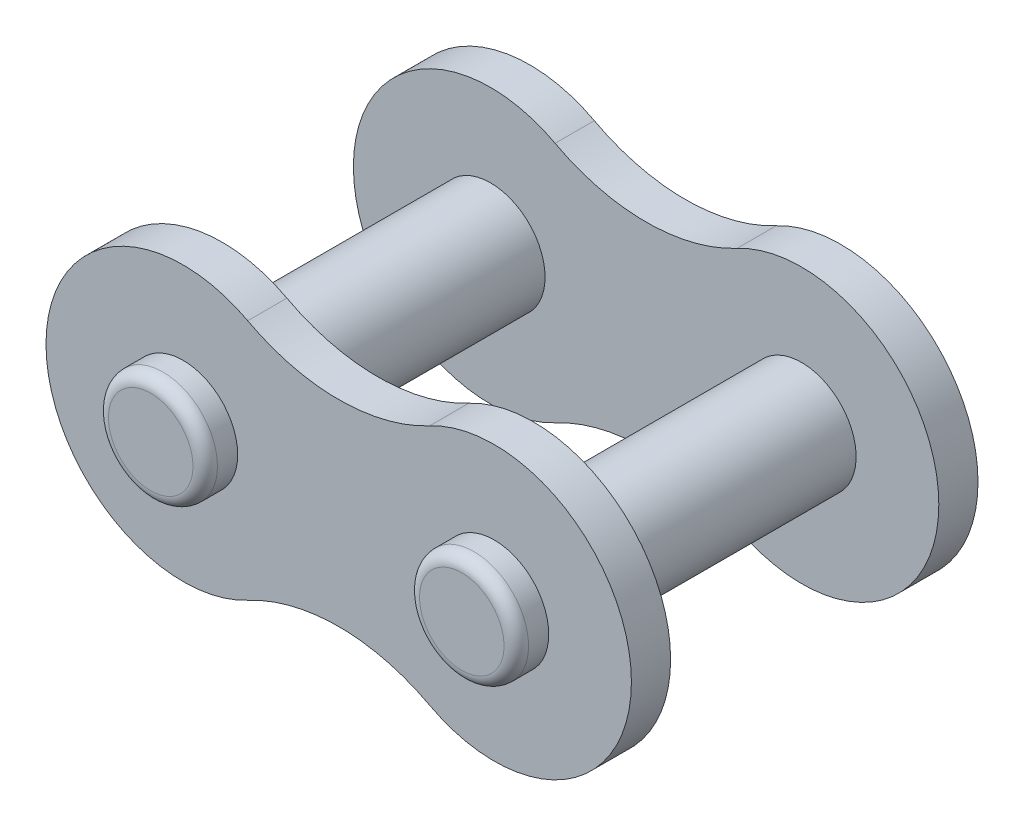
SolidWorks part; units mm, degrees
ref_plane "Front Plane" through (0, 0, 0) normal (0, 0, 1) x (1, 0, 0)
ref_plane "Top Plane" through (0, 0, 0) normal (0, 1, 0) x (1, 0, 0)
ref_plane "Right Plane" through (0, 0, 0) normal (1, 0, 0) x (0, 0, -1)
ref_axis "Axis_X" through (-19.495, 0, 0) along (1, 0, 0)
ref_axis "Axis_Y" through (0, 6.16, 0) along (0, -1, 0)
ref_axis "Axis_Z" through (0, 0, -9.24) along (0, 0, 1)
sketch "Sketch1" plane through (0, 0, 0) normal (0, 1, 0) x (1, 0, 0)
  line L0 (0, 0) -> (0, 8.4) construction
  line L1 (0, -8.4) -> (0, 8.4)
  line L2 (0, 8.4) -> (1.725, 8.4)
  line L3 (2.225, 7.9) -> (2.225, -7.9)
  line L4 (1.725, -8.4) -> (0, -8.4)
  line L5 (0, 0) -> (2.225, 0) construction
  arc A0 (2.225, 7.9) -> (1.725, 8.4) centre (1.725, 7.9) ccw
  arc A1 (1.725, -8.4) -> (2.225, -7.9) centre (1.725, -7.9) ccw
  point P9 (2.225, 8.4)
  dimension "FIX_42" = 0.5
  dimension "FIX_43" = 0.5
  dimension "FIX_41" = 4.45
  dimension "FIX_44" = 16.8
revolve "Revolve1" add sketch "Sketch1" angle 360 about axis through (0, 0, -9.24) along (0, 0, 1)
sketch "Sketch2" plane through (0, 0, 0) normal (0, -1, 0) x (1, 0, 0)
  line L0 (-12.7, 8.4) -> (-12.7, -8.4) construction
  line L1 (-12.7, 8.4) -> (-14.425, 8.4)
  line L2 (-14.925, 7.9) -> (-14.925, -7.9)
  line L3 (-14.425, -8.4) -> (-12.7, -8.4)
  line L4 (-12.7, -8.4) -> (-12.7, 8.4)
  line L5 (0, 0) -> (-12.7, 0) construction
  arc A0 (-14.925, -7.9) -> (-14.425, -8.4) centre (-14.425, -7.9) ccw
  arc A1 (-14.925, 7.9) -> (-14.425, 8.4) centre (-14.425, 7.9) cw
  dimension "FIX_47" = 0.5
  dimension "FIX_49" = 0.5
  dimension "FIX_46" = 4.45
  dimension "FIX_48" = 12.7
  dimension "FIX_50" = 16.8
revolve "Revolve2" add sketch "Sketch2" angle 360 about L0
ref_plane "Plane1" through (0, 0, -5.475) normal (0, 0, 1) x (1, 0, 0)
sketch "Sketch3" plane through (0, 0, -5.475) normal (0, 0, -1) x (0, -1, 0)
  line L0 (0, 0) -> (0, 12.7) construction
  line L1 (-5.6, 0) -> (5.6, 0) construction
  arc A0 (-4.9412, 2.6352) -> (4.9412, 2.6352) centre (0, 0) ccw
  arc A1 (4.9412, 10.0648) -> (-4.9412, 10.0648) centre (0, 12.7) ccw
  circle A2 centre (0, 0) radius 2.225
  circle A3 centre (0, 12.7) radius 2.225
  arc A4 (4.9412, 10.0648) -> (4.9412, 2.6352) centre (11.9065, 6.35) ccw
  arc A5 (-4.9412, 10.0648) -> (-4.9412, 2.6352) centre (-11.9065, 6.35) cw
  dimension "FIX_53" = 4.45
  dimension "FIX_54" = 7.894
  dimension "FIX_55" = 11.2
extrude "Boss-Extrude1" add sketch "Sketch3" along normal blind 1.6
mirror "Mirror1" about plane through (0, 0, 0) normal (0, 0, 1) of "Boss-Extrude1"
equation "\"Factor\"= 1.082532"
